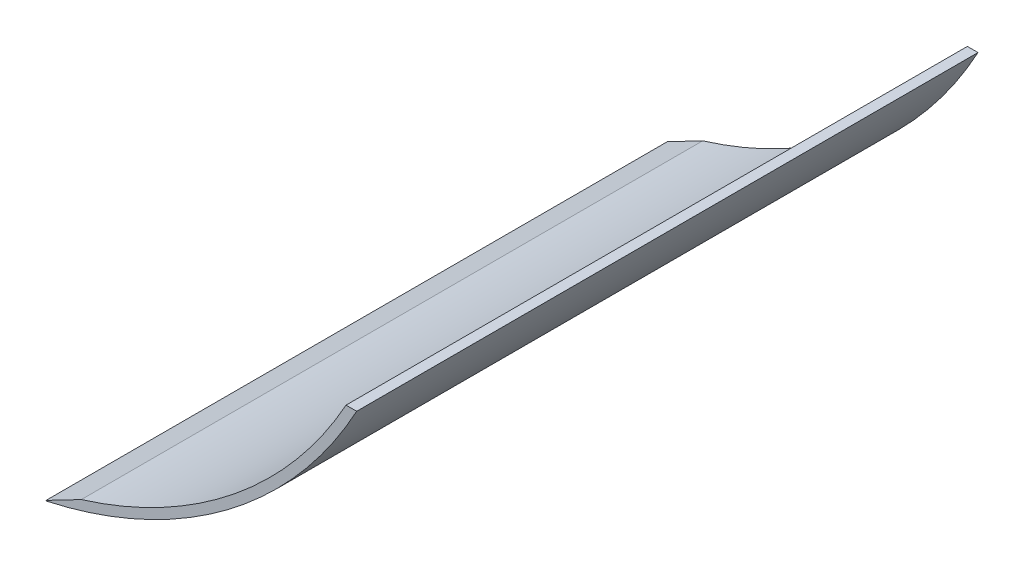
SolidWorks part; units mm, degrees
ref_plane "Front Plane" through (0, 0, 0) normal (0, 0, 1) x (1, 0, 0)
ref_plane "Top Plane" through (0, 0, 0) normal (0, 1, 0) x (1, 0, 0)
ref_plane "Right Plane" through (0, 0, 0) normal (1, 0, 0) x (0, 0, -1)
sketch "Sketch1" plane through (0, 0, 0) normal (0, 0, 1) x (1, 0, 0)
  line L0 (100, 75) -> (96.5758, 75)
  line L1 (0, 0) -> (0, 3.0713)
  arc A0 (0, 0) -> (100, 75) centre (-31.8153, 146.5871) ccw
  arc A1 (0, 3.0713) -> (96.5758, 75) centre (-31.8153, 146.5871) ccw
  arc A2 (-0.6363, 2.9317) -> (97.3637, 76.4317) centre (-31.8153, 146.5871) ccw construction
  point P0 (0, 0)
  point P1 (100, 75)
  dimension "D3" = 150
  dimension "D1" = 100
  dimension "D2" = 75
  dimension "D4" = 3
extrude "Boss-Extrude1" add sketch "Sketch1" along normal blind 200
chamfer "Chamfer1" distance 10 angle 15 1 edges at (0, 3.0713, 100) first distance on face at (52.1395, 33.8643, 100)
